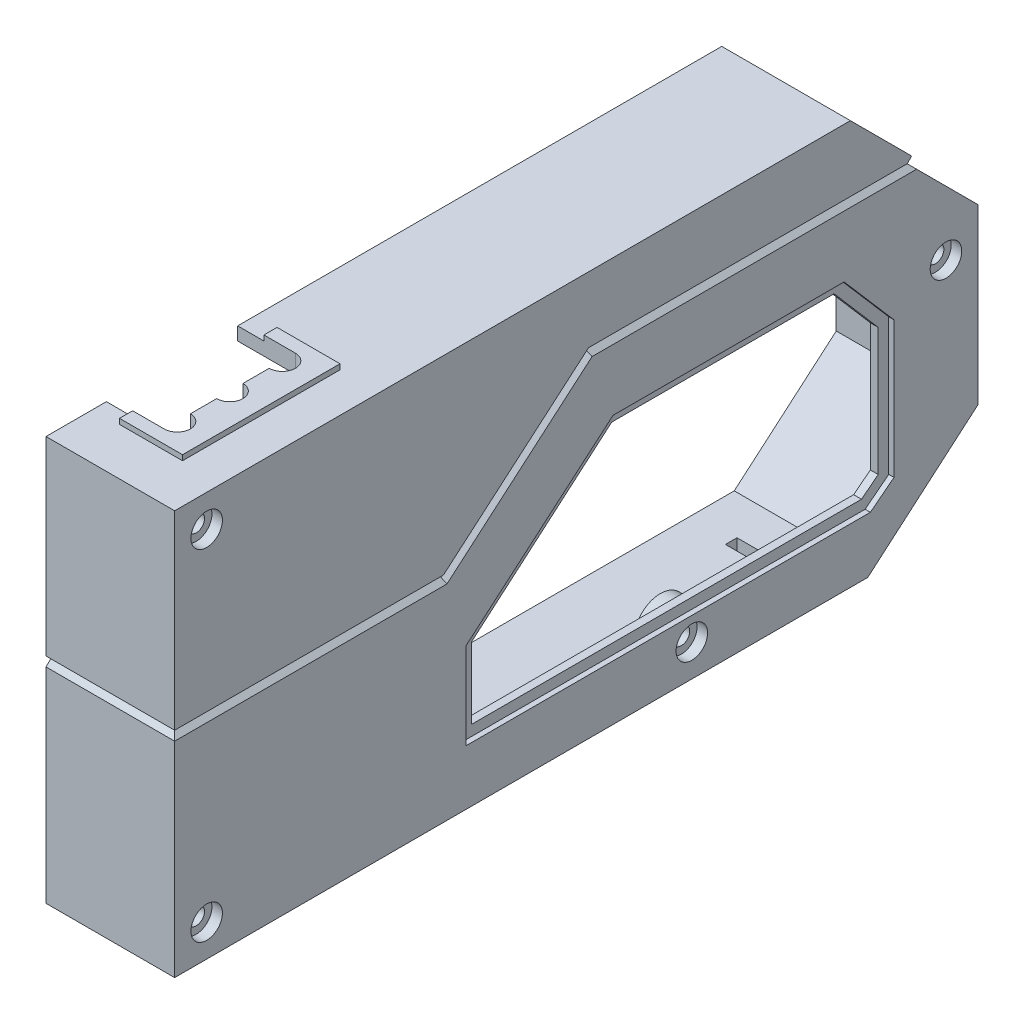
SolidWorks part; units mm, degrees
ref_plane "Front Plane" through (0, 0, 0) normal (0, 0, 1) x (1, 0, 0)
ref_plane "Top Plane" through (0, 0, 0) normal (0, 1, 0) x (1, 0, 0)
ref_plane "Right Plane" through (0, 0, 0) normal (1, 0, 0) x (0, 0, -1)
sketch "Sketch1" plane through (0, 0, 0) normal (1, 0, 0) x (0, 0, -1)
  line L0 (0, 0) -> (0, 77)
  line L1 (0, 77) -> (127, 77)
  line L2 (127, 77) -> (153, 51)
  line L3 (153, 51) -> (153, 18)
  line L4 (153, 18) -> (132, 0)
  line L5 (132, 0) -> (0, 0)
  dimension "D1" = 132
  dimension "D2" = 77
  dimension "D3" = 26
  dimension "D4" = 26
  dimension "D5" = 153
  dimension "D6" = 18
extrude "Base" add sketch "Sketch1" along normal blind 2.5
sketch "Sketch11" plane through (0, 0, 0) normal (-1, 0, 0) x (0, 0, 1)
  line L12 (-131.0752, 2.5) -> (-2.5, 2.5)
  line L13 (-2.5, 2.5) -> (-2.5, 74.5)
  line L14 (-2.5, 74.5) -> (-125.9645, 74.5)
  line L15 (-125.9645, 74.5) -> (-150.5, 49.9645)
  line L16 (-150.5, 49.9645) -> (-150.5, 19.1498)
  line L17 (-150.5, 19.1498) -> (-131.0752, 2.5)
  line L18 (-131.0752, 2.5) -> (-2.5, 2.5)
  line L19 (-2.5, 2.5) -> (-2.5, 74.5)
  line L20 (-2.5, 74.5) -> (-125.9645, 74.5)
  line L21 (-125.9645, 74.5) -> (-150.5, 49.9645)
  line L22 (-150.5, 49.9645) -> (-150.5, 19.1498)
  line L23 (-150.5, 19.1498) -> (-131.0752, 2.5)
  line M7 (-132, 0) -> (0, 0)
  line M8 (0, 0) -> (0, 77)
  line M9 (0, 77) -> (-127, 77)
  line M10 (-127, 77) -> (-153, 51)
  line M11 (-153, 51) -> (-153, 18)
  line M12 (-153, 18) -> (-132, 0)
  dimension "D1" = 2.5
extrude "Boss-Extrude6" add sketch "Sketch11" along normal blind 22 contours L23 L22 L21 L20 L19 L18 M12 M7 M8 M9 M10 M11 region at (0, 10.3005, -141.3853)
ref_plane "Middle" through (-11, 0, 0) normal (1, 0, 0) x (0, 0, -1)
sketch "Sketch17" plane through (0, 77, 0) normal (0, 1, 0) x (1, 0, 0)
  line L5 (-11, -42.35) -> (-11, 42.35) construction
  line L6 (-5, 39) -> (-17, 39)
  line L7 (-5, 39) -> (-5, 9)
  line L8 (-5, 9) -> (-17, 9)
  line L9 (-17, 39) -> (-17, 9)
  line L10 (-5, 39) -> (-17, 9) construction
  line L11 (-5, 9) -> (-17, 39) construction
  line L12 (2.5, 0) -> (-22, 0) construction
  point P0 (-11, 24)
  dimension "D1" = 12
  dimension "D2" = 30
  dimension "D3" = 24
extrude "Boss-Extrude8" add sketch "Sketch17" along normal blind 1
sketch "Sketch13" plane through (0, 78, 0) normal (0, 1, 0) x (1, 0, 0)
  line L0 (-22, 11.5) -> (-11, 11.5)
  line L1 (-22, 0) -> (-22, 127) construction
  line L2 (-11, 16.5) -> (-11, 21.5)
  line L3 (-11, 26.5) -> (-11, 31.5)
  line L4 (-11, 36.5) -> (-22, 36.5)
  line L5 (-22, 36.5) -> (-22, 11.5)
  line L6 (-5, 9) -> (-5, 39) construction
  line L7 (-11, -42.35) -> (-11, 42.35) construction
  arc A0 (-11, 11.5) -> (-11, 16.5) centre (-11, 14) ccw
  arc A1 (-11, 21.5) -> (-11, 26.5) centre (-11, 24) ccw
  arc A2 (-11, 31.5) -> (-11, 36.5) centre (-11, 34) ccw
  point P9 (-5, 24)
  dimension "D1" = 5
  dimension "D4" = 10
  dimension "D5" = 10
extrude "Cut-Extrude2" cut sketch "Sketch13" against normal up to next
sketch "Sketch19" plane through (2.5, 0, 0) normal (1, 0, 0) x (0, 0, -1)
  line L0 (127, 77) -> (128.6971, 77)
  line L1 (128.6971, 77) -> (140.3643, 65.3327)
  line L2 (140.3643, 65.3327) -> (139.5158, 64.4842)
  line L3 (153, 51) -> (127, 77) construction
  line L4 (139.5158, 64.4842) -> (127, 77)
  dimension "D1" = 1.2
  dimension "D2" = 16.5
extrude "Boss-Extrude9" add sketch "Sketch19" against normal up to vertex (24.5 mm away) up to point (-22, 77, -127)
sketch "Sketch20" plane through (0, 102.8485, -102.8485) normal (0, 0.7071, -0.7071) x (-1, 0, 0)
  line L1 (11, 42.35) -> (11, -42.35) construction
  line L2 (2.5, -53.0553) -> (19.5, -53.0553)
  line L3 (2.5, -53.0553) -> (2.5, -44.5553)
  line L4 (2.5, -44.5553) -> (19.5, -44.5553)
  line L5 (19.5, -53.0553) -> (19.5, -44.5553)
  line L6 (2.5, -53.0553) -> (19.5, -44.5553) construction
  line L7 (2.5, -44.5553) -> (19.5, -53.0553) construction
  line L8 (-2.5, -53.0553) -> (-2.5, -36.5553) construction
  line L9 (22, -36.5553) -> (-2.5, -36.5553) construction
  line L10 (22, -53.0553) -> (-2.5, -53.0553) construction
  point P2 (11, -48.8053)
  dimension "D1" = 5
  dimension "D2" = 8
extrude "Cut-Extrude5" cut sketch "Sketch20" against normal up to vertex (1.2 mm away) up to point (2.5, 64.4842, -139.5158)
sketch "Sketch21" plane through (0, 102, -102) normal (0, 0.7071, -0.7071) x (-1, 0, 0)
  line L0 (11, 48.4) -> (11, -48.4) construction
  line L1 (19.5, -44.5553) -> (2.5, -44.5553) construction
  line L2 (11, -48.0053) -> (22, -48.0053)
  line L3 (22, -48.0053) -> (22, -53.1053)
  line L4 (22, -53.0553) -> (22, -72.1249) construction
  line L5 (11, -53.1053) -> (22, -53.1053)
  line L6 (22, 44.5477) -> (22, 46.3155) construction
  arc A0 (11, -48.0053) -> (11, -53.1053) centre (11, -50.5553) ccw
  dimension "D1" = 5.1
  dimension "D2" = 6
extrude "Cut-Extrude6" cut sketch "Sketch21" against normal mid plane 10
sketch "Sketch28" plane through (2.5, 0, 0) normal (1, 0, 0) x (0, 0, -1)
  circle A0 centre (6.1, 70.9) radius 5
  circle A1 centre (146.9, 44.9) radius 5
  circle A2 centre (98.5, 6.1) radius 5
  circle A3 centre (6.1, 6.1) radius 5
  dimension "D9" = 10
  dimension "D1" = 6.1
  dimension "D2" = 6.1
  dimension "D3" = 70.9
  dimension "D4" = 6.1
  dimension "D5" = 98.5
  dimension "D6" = 6.1
  dimension "D7" = 44.9
  dimension "D8" = 146.9
extrude "Boss-Extrude11" add sketch "Sketch28" against normal blind 6
sketch "Sketch29" plane through (2.5, 0, 0) normal (1, 0, 0) x (0, 0, -1)
  circle A0 centre (6.1, 70.9) radius 3
  circle A1 centre (146.9, 44.9) radius 3
  circle A2 centre (98.5, 6.1) radius 3
  circle A3 centre (6.1, 6.1) radius 3
  dimension "D1" = 6
extrude "Cut-Extrude11" cut sketch "Sketch29" against normal blind 2
sketch "Sketch30" plane through (0.5, 0, 0) normal (1, 0, 0) x (0, 0, -1)
  circle A0 centre (6.1, 70.9) radius 1.6
  circle A1 centre (6.1, 6.1) radius 1.6
  circle A2 centre (146.9, 44.9) radius 1.6
  circle A3 centre (98.5, 6.1) radius 1.6
  dimension "D1" = 3.2
extrude "Cut-Extrude12" cut sketch "Sketch30" against normal up to next
sketch "Sketch31" plane through (0, 0, 0) normal (-1, 0, 0) x (0, 0, 1)
  line L1 (-14.5, 47.5) -> (-4.5, 47.5)
  line L2 (-14.5, 47.5) -> (-14.5, 22.5)
  line L3 (-14.5, 22.5) -> (-4.5, 22.5)
  line L4 (-4.5, 47.5) -> (-4.5, 22.5)
  line L5 (-14.5, 47.5) -> (-4.5, 22.5) construction
  line L6 (-14.5, 22.5) -> (-4.5, 47.5) construction
  point P0 (-9.5, 35)
  dimension "D1" = 9.5
  dimension "D2" = 35
  dimension "D3" = 25
  dimension "D4" = 10
extrude "Battery_Support" add sketch "Sketch31" along normal blind 3.4
sketch "Sketch25" plane through (2.5, 0, 0) normal (1, 0, 0) x (0, 0, -1)
  line L0 (55.5, 10.5) -> (132.5, 10.5)
  line L1 (132.5, 10.5) -> (137, 14)
  line L2 (137, 14) -> (137, 40)
  line L3 (137, 40) -> (127.5, 51)
  line L4 (127.5, 51) -> (83.5, 51)
  line L5 (83.5, 51) -> (55.5, 27)
  line L6 (55.5, 27) -> (55.5, 10.5)
  dimension "D1" = 77
  dimension "D2" = 4.5
  dimension "D3" = 3.5
  dimension "D4" = 72
  dimension "D5" = 26
  dimension "D6" = 10.5
  dimension "D7" = 55.5
  dimension "D8" = 40.5
  dimension "D9" = 28
  dimension "D10" = 16.5
extrude "Cut-Extrude9" cut sketch "Sketch25" against normal blind 1
sketch "Sketch26" plane through (1.5, 0, 0) normal (1, 0, 0) x (0, 0, -1)
  line L14 (57.5, 26.0801) -> (57.5, 12.5)
  line L15 (57.5, 12.5) -> (131.8138, 12.5)
  line L16 (131.8138, 12.5) -> (135, 14.9782)
  line L17 (135, 14.9782) -> (135, 39.2559)
  line L18 (135, 39.2559) -> (126.5846, 49)
  line L19 (126.5846, 49) -> (84.2398, 49)
  line L20 (84.2398, 49) -> (57.5, 26.0801)
  line L21 (57.5, 26.0801) -> (57.5, 12.5)
  line L22 (57.5, 12.5) -> (131.8138, 12.5)
  line L23 (131.8138, 12.5) -> (135, 14.9782)
  line L24 (135, 14.9782) -> (135, 39.2559)
  line L25 (135, 39.2559) -> (126.5846, 49)
  line L26 (126.5846, 49) -> (84.2398, 49)
  line L27 (84.2398, 49) -> (57.5, 26.0801)
  dimension "D1" = 2
extrude "Cut-Extrude10" cut sketch "Sketch26" against normal up to next
sketch "Sketch32" plane through (2.5, 0, 0) normal (1, 0, 0) x (0, 0, -1)
  line L0 (144.5158, 63.6842) -> (79.1216, 63.6842)
  line L1 (79.1216, 63.6842) -> (51.49, 40)
  line L2 (51.49, 40) -> (0, 40)
  line L3 (0, 77) -> (0, 0) construction
  line L4 (83.5, 51) -> (55.5, 27) construction
  line L5 (144.5158, 63.6842) -> (144.5158, 64.4842)
  line L6 (144.5158, 64.4842) -> (78.8257, 64.4842)
  line L7 (78.8257, 64.4842) -> (51.1941, 40.8)
  line L8 (51.1941, 40.8) -> (0, 40.8)
  line L9 (0, 40.8) -> (0, 40)
  dimension "D1" = 0.8
  dimension "D2" = 0.8
  dimension "D3" = 0.8
  dimension "D4" = 5
  dimension "D5" = 12.48
  dimension "D6" = 40
extrude "Cut-Extrude13" cut sketch "Sketch32" against normal blind 1
sketch "Sketch33" plane through (0, 0, 0) normal (0, 0, 1) x (1, 0, 0)
  line L0 (-22, 0) -> (-22, 77) construction
  line L1 (1.5, 40.8) -> (-22, 40.8)
  line L2 (1.5, 40.8) -> (1.5, 40)
  line L3 (1.5, 40) -> (-22, 40)
  line L4 (-22, 40.8) -> (-22, 40)
extrude "Cut-Extrude14" cut sketch "Sketch33" against normal blind 1
chamfer "Chamfer1" distance 1 angle 45 4 edges at (-9.75, 40, 0) (2.5, 40, -25.745) (2.5, 51.8421, -65.3058) (2.5, 63.6842, -109.7187)
sketch "Sketch23" plane through (0, 0, 0) normal (0, -1, 0) x (1, 0, 0)
  line L0 (-11, -42.9) -> (-11, 42.9) construction
  line L2 (-8, -10.5) -> (-14, -10.5)
  line L3 (-8, -10.5) -> (-8, -8.3)
  line L4 (-8, -123.6) -> (-14, -123.6)
  line L5 (-5.5, -10.5) -> (-16.5, -10.5)
  line L6 (-5.5, -10.5) -> (-5.5, -60.5)
  line L7 (-5.5, -60.5) -> (-16.5, -60.5)
  line L8 (-16.5, -10.5) -> (-16.5, -60.5)
  line L9 (-8, -123.6) -> (-8, -121.4)
  line L10 (-8, -121.4) -> (-14, -121.4)
  line L11 (-8, -8.3) -> (-14, -8.3)
  line L12 (-14, -10.5) -> (-14, -8.3)
  line L13 (-8, -10.5) -> (-14, -8.3) construction
  line L14 (-8, -8.3) -> (-14, -10.5) construction
  line L15 (-14, -123.6) -> (-14, -121.4)
  line L16 (-8, -123.6) -> (-14, -121.4) construction
  line L17 (-8, -121.4) -> (-14, -123.6) construction
  point P4 (-11, -10.5)
  point P7 (-11, -9.4)
  point P15 (-11, -122.5)
  dimension "D1" = 10.5
  dimension "D2" = 11
  dimension "D3" = 6
  dimension "D4" = 50
  dimension "D5" = 2.2
  dimension "D6" = 6
  dimension "D7" = 2.2
  dimension "D8" = 122.5
extrude "Cut-Extrude7" cut sketch "Sketch23" against normal up to next contours L5 L8 L7 L6 L2 | L12 L2 L3 L11 | L15 L4 L9 L10 region at (-11, 0, -35.5) region at (-11, 0, -9.4) region at (-11, 0, -122.5)
fillet "Fillet1" radius 3.5 10 edges at (0, 10.8249, -140.7876) (0, 2.5, -116.5225) (0, 2.5, -52.3) (0, 9.6355, -9.6355) (0, 38.5, -2.5) (0, 67.3645, -9.6355) (0, 44.9, -141.9) (0, 30.29, -150.5) (0, 62.2322, -138.2322) (0, 74.5, -67.7672)
sketch "Sketch34" plane through (0, 0, 0) normal (-1, 0, 0) x (0, 0, 1)
  line L0 (-33.1656, 58.3489) -> (-33.1656, 62.9806)
  line L1 (-17.9256, 66.3611) -> (-17.9256, 51.1211)
  line L2 (-17.9256, 51.1211) -> (-24.2127, 51.1211)
  spline S0 degree 3 poles (-24.2127, 51.1211) (-24.5454, 51.7372) (-25.0939, 52.3164) (-25.63, 52.799) knots 0 0 0 0 1 1 1 1
  spline S1 degree 3 poles (-25.63, 52.799) (-26.2766, 53.1332) (-26.8806, 53.543) (-27.514, 53.9251) knots 0 0 0 0 1 1 1 1
  spline S2 degree 3 poles (-27.514, 53.9251) (-28.1542, 54.2808) (-28.7225, 54.7569) (-29.3119, 55.2165) knots 0 0 0 0 1 1 1 1
  spline S3 degree 3 poles (-29.3119, 55.2165) (-29.8742, 55.6744) (-30.5484, 55.9491) (-31.0783, 56.4581) knots 0 0 0 0 1 1 1 1
  spline S4 degree 3 poles (-31.0783, 56.4581) (-31.6251, 56.9085) (-32.1256, 57.391) (-32.6302, 57.8712) knots 0 0 0 0 1 1 1 1
  spline S5 degree 3 poles (-32.6302, 57.8712) (-32.7307, 58.1967) (-33.0299, 58.2171) (-33.1656, 58.3489) knots 0 0 0 0 1 1 1 1
  spline S6 degree 3 poles (-33.1656, 62.9806) (-32.4827, 63.0469) (-31.9187, 63.5329) (-31.2006, 63.5365) knots 0 0 0 0 1 1 1 1
  spline S7 degree 3 poles (-31.2006, 63.5365) (-30.4319, 63.5402) (-29.751, 63.908) (-28.9909, 63.9555) knots 0 0 0 0 1 1 1 1
  spline S8 degree 3 poles (-28.9909, 63.9555) (-28.2121, 63.9876) (-27.5343, 64.4022) (-26.8176, 64.645) knots 0 0 0 0 1 1 1 1
  spline S9 degree 3 poles (-26.8176, 64.645) (-26.145, 65.0212) (-25.2929, 64.901) (-24.596, 65.2096) knots 0 0 0 0 1 1 1 1
  spline S10 degree 3 poles (-24.596, 65.2096) (-23.8998, 65.447) (-23.1367, 65.4331) (-22.4727, 65.7592) knots 0 0 0 0 1 1 1 1
  spline S11 degree 3 poles (-22.4727, 65.7592) (-21.4003, 65.9292) (-20.269, 65.8385) (-19.2593, 66.2914) knots 0 0 0 0 1 1 1 1
  spline S12 degree 3 poles (-19.2593, 66.2914) (-18.8198, 66.3692) (-18.3701, 66.3416) (-17.9256, 66.3611) knots 0 0 0 0 1 1 1 1
  spline S14 degree 3 poles (-22.6787, 54.1861) (-22.1169, 54.3881) (-20.7979, 53.868) (-20.8369, 54.7283) knots 0 0 0 0 1 1 1 1
  spline S15 degree 3 poles (-20.8369, 54.7283) (-21.3748, 55.1866) (-22.2388, 55.4073) (-22.981, 55.4632) knots 0 0 0 0 1 1 1 1
  spline S16 degree 3 poles (-22.981, 55.4632) (-23.6328, 55.3358) (-24.8449, 55.7175) (-24.9541, 54.8085) knots 0 0 0 0 1 1 1 1
  spline S17 degree 3 poles (-24.9541, 54.8085) (-25.1031, 53.8538) (-23.9123, 54.2071) (-23.3427, 54.1663) knots 0 0 0 0 1 1 1 1
  spline S18 degree 3 poles (-23.3427, 54.1663) (-23.1214, 54.1727) (-22.9, 54.1794) (-22.6787, 54.1861) knots 0 0 0 0 1 1 1 1
  spline S19 degree 3 poles (-21.3533, 58.6329) (-20.7123, 59.0861) (-20.6887, 59.9631) (-20.7711, 60.6729) knots 0 0 0 0 1 1 1 1
  spline S20 degree 3 poles (-20.7711, 60.6729) (-21.0484, 61.3149) (-21.6447, 61.9637) (-22.4425, 61.7934) knots 0 0 0 0 1 1 1 1
  spline S21 degree 3 poles (-22.4425, 61.7934) (-23.2222, 61.5245) (-23.1071, 60.638) (-23.091, 59.9818) knots 0 0 0 0 1 1 1 1
  spline S22 degree 3 poles (-23.091, 59.9818) (-23.1727, 59.2502) (-22.5154, 58.5831) (-21.813, 58.5489) knots 0 0 0 0 1 1 1 1
  spline S23 degree 3 poles (-21.813, 58.5489) (-21.6582, 58.5589) (-21.4906, 58.5443) (-21.3533, 58.6329) knots 0 0 0 0 1 1 1 1
extrude "Cut-Extrude15" cut sketch "Sketch34" against normal blind 0.2
equation "\"D5@Sketch13\"=\"D4@Sketch13\""
equation "\"D2@Sketch32\"=\"D1@Sketch32\""
equation "\"D3@Sketch32\"=\"D1@Sketch32\""
